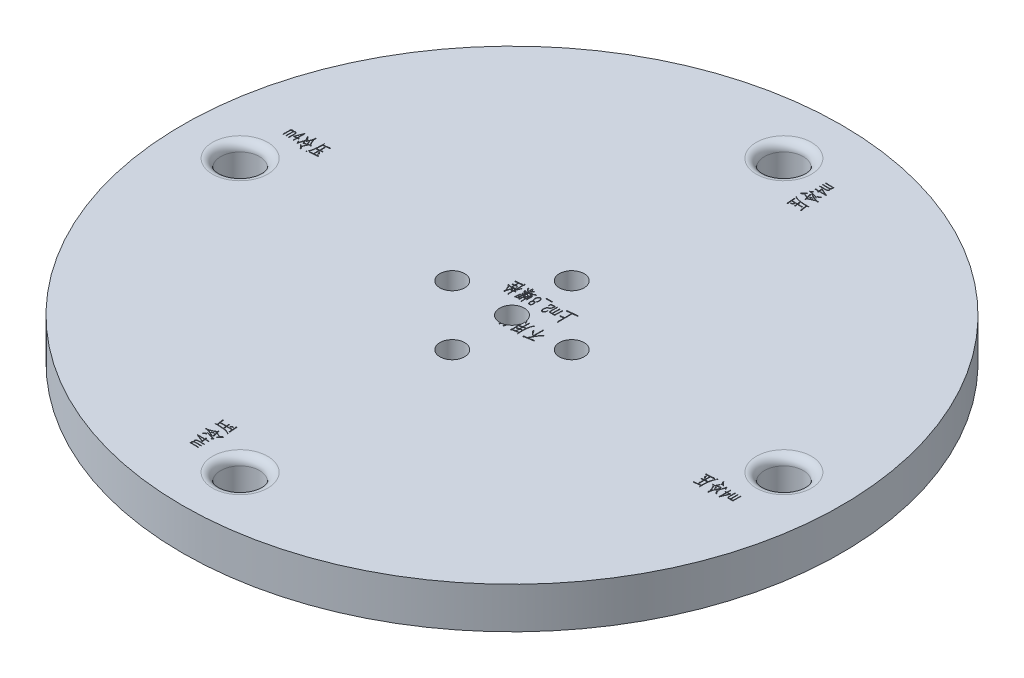
SolidWorks part; units mm, degrees
ref_plane "前视基准面" through (0, 0, 0) normal (0, 0, 1) x (1, 0, 0)
ref_plane "上视基准面" through (0, 0, 0) normal (0, 1, 0) x (1, 0, 0)
ref_plane "右视基准面" through (0, 0, 0) normal (1, 0, 0) x (0, 0, -1)
sketch "草图1" plane through (0, 0, 0) normal (0, 1, 0) x (1, 0, 0)
  line L14 (0, 0) -> (35, 0)
  line L15 (0, 0) -> (0, -35)
  circle A0 centre (0, 0) radius 40
  circle A5 centre (0, 0) radius 35
  circle A6 centre (0, 0) radius 34
  circle A7 centre (0, -34) radius 1
  circle A8 centre (0, -33) radius 2
  dimension "D1" = 80
  dimension "D2" = 70
  dimension "D3" = 68
sketch "草图3" plane through (0, 0, 0) normal (0, 1, 0) x (1, 0, 0)
  circle A0 centre (0, -33) radius 2 construction
  circle A1 centre (0, -33) radius 2
  circle A2 centre (0, 0) radius 33
  circle A3 centre (-32.999, 0.001) radius 2
  circle A4 centre (0.002, 33) radius 2
  circle A5 centre (33.001, -0.001) radius 2
  point P15 (0.001, 0)
  dimension "D2" = 4
  dimension "D1" = 4
sketch "草图4" plane through (0, 0, 0) normal (0, 1, 0) x (1, 0, 0)
  circle A0 centre (0, 0) radius 40 construction
  circle A1 centre (0, 0) radius 40
extrude "凸台-拉伸1" add sketch "草图4" along normal blind 5
sketch "草图6" plane through (0, 0, 0) normal (0, 1, 0) x (1, 0, 0)
  circle A14 centre (0.002, 33) radius 2 construction
  circle A16 centre (-32.999, 0.001) radius 2.35
  circle A17 centre (0, -33) radius 2.35
  circle A18 centre (33.001, -0.001) radius 2.35
  circle A19 centre (0.002, 33) radius 2.35
  dimension "D2" = 4.7
extrude "固定轴承内圈的四个冷压孔" cut sketch "草图6" along normal up to surface (5 mm away) up to face at (0, 5, 40)
fillet "圆角1" radius 1 4 edges at (0.002, 5, -30.65) (33.001, 5, 2.351) (0, 5, 35.35) (-32.999, 5, 2.349)
ref_plane "基准面1" through (0, 5, 0) normal (0, 1, 0) x (1, 0, 0)
sketch "草图8" plane through (0, 5, 0) normal (0, 1, 0) x (1, 0, 0)
  line L0 (0.002, 33) -> (-32.999, 0.001)
  line L1 (0.002, 33) -> (33.001, -0.001)
  line L2 (-32.999, 0.001) -> (0, -33)
  line L3 (33.001, -0.001) -> (0, -33)
  line L5 (33.001, -0.001) -> (28.0007, -0.001)
  line L6 (33.001, -0.001) -> (33.001, -5.001)
  line L7 (33.001, -5.001) -> (28.0007, -5.001)
  line L8 (28.0007, -0.001) -> (28.0007, -5.001)
  line L9 (0.002, 33) -> (5.002, 33)
  line L10 (0.002, 33) -> (0.002, 27.9997)
  line L11 (0.002, 27.9997) -> (5.002, 27.9997)
  line L12 (5.002, 33) -> (5.002, 27.9997)
  line L13 (-32.999, 0.001) -> (-27.9987, 0.001)
  line L14 (-32.999, 0.001) -> (-32.999, 5.001)
  line L15 (-32.999, 5.001) -> (-27.9987, 5.001)
  line L16 (-27.9987, 0.001) -> (-27.9987, 5.001)
  line L17 (0, -33) -> (-5, -33)
  line L18 (0, -33) -> (0, -27.9997)
  line L19 (0, -27.9997) -> (-5, -27.9997)
  line L20 (-5, -33) -> (-5, -27.9997)
  circle A0 centre (0, 0) radius 33
  circle A1 centre (-32.999, 0.001) radius 2.35 construction
  circle A2 centre (-32.999, 0.001) radius 2.35
  circle A3 centre (0.002, 33) radius 2.35 construction
  circle A4 centre (0.002, 33) radius 2.35
  circle A5 centre (0, -33) radius 2.35 construction
  circle A6 centre (0, -33) radius 2.35
  circle A7 centre (0, 0) radius 40 construction
  circle A8 centre (0, 0) radius 40
  dimension "D1" = 5
  dimension "D5" = 66
  dimension "D6" = 80
  dimension "D2" = 5
  dimension "D3" = 5
  dimension "D4" = 5
sketch "草图9" plane through (0, 5, 0) normal (0, 1, 0) x (1, 0, 0)
  text T0 "m4冷压" font "汉仪长仿宋体" height 1.5
  text T1 "m4冷压" font "汉仪长仿宋体" height 1.5
  text T2 "m4冷压" font "汉仪长仿宋体" height 1.5
  text T3 "m4冷压\r\n" font "汉仪长仿宋体" height 1.5
extrude "切除-拉伸1" cut sketch "草图9" against normal blind 0.5
ref_plane "基准面2" through (0, 5, 0) normal (0, 1, 0) x (1, 0, 0)
sketch "草图12" plane through (0, 5, 0) normal (0, 1, 0) x (1, 0, 0)
  text T0 "不用管\r\n上m2_8螺栓" font "汉仪长仿宋体" height 1.5
extrude "切除-拉伸7" cut sketch "草图12" against normal blind 0.5
sketch "草图13" plane through (0, 5, 0) normal (0, 1, 0) x (1, 0, 0)
  circle A0 centre (0, 0) radius 10
sketch "草图14" plane through (0, 5, 0) normal (0, 1, 0) x (1, 0, 0)
  circle A0 centre (0, 0) radius 10
  circle A1 centre (0, 7.25) radius 1.5
  circle A2 centre (7.249, -0.001) radius 1.5
  circle A3 centre (-7.251, 0.001) radius 1.5
  circle A4 centre (0, 0) radius 1.5
  circle A5 centre (-0.002, -7.25) radius 1.5
sketch "草图15" plane through (0, 5, 0) normal (0, 1, 0) x (1, 0, 0)
  circle A1 centre (-0.002, -7.25) radius 1.5
  circle A2 centre (-0.002, -7.25) radius 1.5
  circle A3 centre (0, 0) radius 1.5
  circle A4 centre (0, 0) radius 1.5
  circle A5 centre (-7.251, 0.001) radius 1.5
  circle A6 centre (-7.251, 0.001) radius 1.5
  circle A7 centre (7.249, -0.001) radius 1.5
  circle A8 centre (7.249, -0.001) radius 1.5
  circle A9 centre (0, 7.25) radius 1.5
  circle A10 centre (0, 7.25) radius 1.5
  dimension "D1" = 0
  dimension "D2" = 0
  dimension "D3" = 0
  dimension "D4" = 0
  dimension "D5" = 0
extrude "切除-拉伸8" cut sketch "草图15" against normal up to surface (5 mm away) up to face at (-32.999, 0, 2.349)
